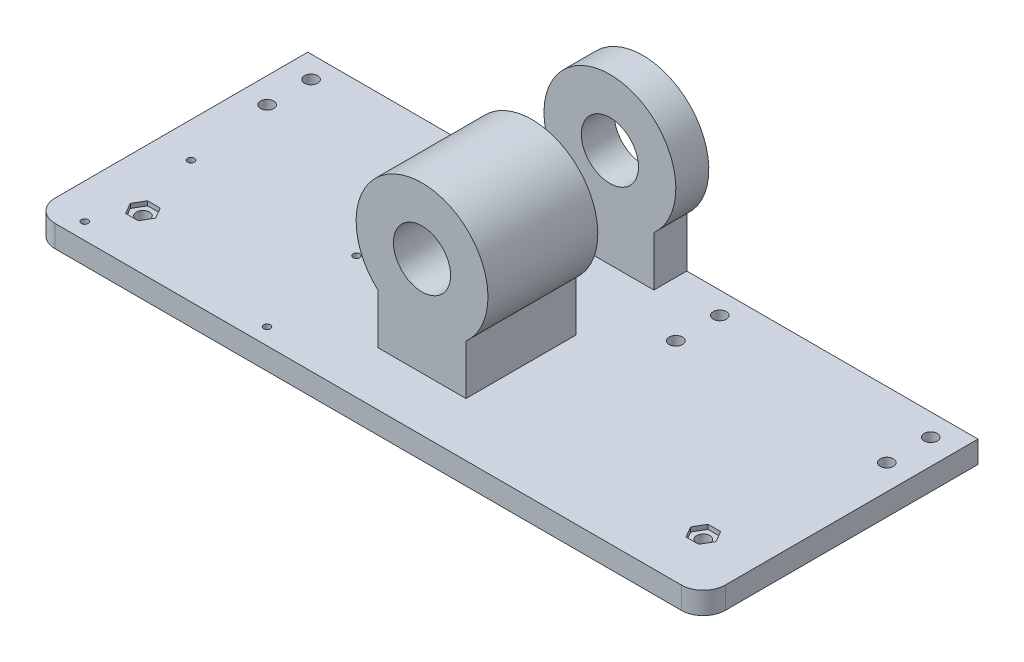
SolidWorks part; units mm, degrees
ref_plane "Front Plane" through (0, 0, 0) normal (0, 0, 1) x (1, 0, 0)
ref_plane "Top Plane" through (0, 0, 0) normal (0, 1, 0) x (1, 0, 0)
ref_plane "Right Plane" through (0, 0, 0) normal (1, 0, 0) x (0, 0, -1)
sketch "Sketch1" plane through (0, 0, 0) normal (0, 1, 0) x (1, 0, 0)
  line L0 (152.5, 125) -> (152.5, 0) construction
  line L1 (0, 0) -> (305, 0)
  line L2 (0, 0) -> (0, 125)
  line L3 (0, 125) -> (305, 125)
  line L4 (305, 0) -> (305, 125)
  line L5 (25, 100) -> (280, 100) construction
  line L6 (280, 25) -> (280, 100) construction
  line L7 (25, 25) -> (280, 25) construction
  line L8 (25, 25) -> (25, 100) construction
  line L9 (152.5, 62.5) -> (25, 62.5) construction
  line L10 (30.7735, 100) -> (27.8868, 105) construction
  line L11 (27.8868, 105) -> (22.1132, 105) construction
  line L12 (22.1132, 105) -> (19.2265, 100) construction
  line L13 (19.2265, 100) -> (22.1132, 95) construction
  line L14 (22.1132, 95) -> (27.8868, 95) construction
  line L15 (27.8868, 95) -> (30.7735, 100) construction
  line L16 (27.8868, 30) -> (30.7735, 25) construction
  line L17 (22.1132, 30) -> (27.8868, 30) construction
  line L18 (19.2265, 25) -> (22.1132, 30) construction
  line L19 (22.1132, 20) -> (19.2265, 25) construction
  line L20 (27.8868, 20) -> (22.1132, 20) construction
  line L21 (30.7735, 25) -> (27.8868, 20) construction
  line L22 (282.8868, 30) -> (277.1132, 30) construction
  line L23 (285.7735, 25) -> (282.8868, 30) construction
  line L24 (282.8868, 20) -> (285.7735, 25) construction
  line L25 (277.1132, 20) -> (282.8868, 20) construction
  line L26 (274.2265, 25) -> (277.1132, 20) construction
  line L27 (277.1132, 30) -> (274.2265, 25) construction
  line L28 (277.1132, 95) -> (274.2265, 100) construction
  line L29 (282.8868, 95) -> (277.1132, 95) construction
  line L30 (285.7735, 100) -> (282.8868, 95) construction
  line L31 (282.8868, 105) -> (285.7735, 100) construction
  line L32 (277.1132, 105) -> (282.8868, 105) construction
  line L33 (274.2265, 100) -> (277.1132, 105) construction
  line L34 (107.5, 115) -> (107.5, 125) construction
  line L35 (132.5, 0) -> (172.5, 0) construction
  line L37 (132.5, 125) -> (172.5, 125) construction
  line L41 (132.5, 25) -> (172.5, 25) construction
  line L50 (305, 14.5) -> (253.3, 14.5) construction
  line L51 (30.7735, 100) -> (22.1132, 105) construction
  line L54 (0, 125) -> (90.0836, 125) construction
  line L55 (0, 125) -> (0, 84.5) construction
  line L62 (0, 84.5) -> (0, 69.5) construction
  line L64 (62, 0) -> (62, 125) construction
  line L65 (253.3, 14.5) -> (253.3, 0) construction
  line L67 (253.3, 14.5) -> (280.2, 14.5) construction
  circle A1 centre (25, 100) radius 5 construction
  circle A3 centre (280, 25) radius 3
  circle A4 centre (25, 25) radius 3
  circle A18 centre (107.5, 115) radius 3
  circle A20 centre (107.5, 95) radius 3
  circle A23 centre (197.5, 115) radius 3
  circle A24 centre (197.5, 95) radius 3
  circle A27 centre (107.5, 75) radius 3 [skipped]
  circle A28 centre (107.5, 55) radius 3 [skipped]
  circle A29 centre (11.5, 95) radius 3
  circle A30 centre (11.5, 115) radius 3
  circle A31 centre (293.5, 115) radius 3
  circle A32 centre (293.5, 95) radius 3
  dimension "D3" = 6
  dimension "D1" = 305
  dimension "D2" = 125
  dimension "D5" = 10
  dimension "D6" = 40
  dimension "D15" = 62
  dimension "D18" = 51.7
  dimension "D19" = 14.5
  dimension "D20" = 26.9
  dimension "D8" = 20
  dimension "D9" = 45
  dimension "D11" = 11.5
  dimension "D4" = 25
  dimension "D14" = 2
  dimension "D7" = 4
  dimension "D10" = 2
extrude "Boss-Extrude1" add sketch "Sketch1" along normal blind 10
sketch "Sketch7" plane through (0, 10, 0) normal (0, 1, 0) x (1, 0, 0)
  line L0 (0, 0) -> (305, 0) construction
  line L1 (132.5, 24.5) -> (172.5, 24.5)
  line L2 (132.5, 24.5) -> (132.5, 74.5)
  line L3 (132.5, 74.5) -> (172.5, 74.5)
  line L4 (172.5, 24.5) -> (172.5, 74.5)
  line L5 (152.5, 0) -> (152.5, 125) construction
  line L6 (305, 125) -> (0, 125) construction
  line L18 (132.5, 110) -> (172.5, 110)
  line L19 (132.5, 110) -> (132.5, 125)
  line L20 (132.5, 125) -> (172.5, 125)
  line L21 (172.5, 110) -> (172.5, 125)
  point P11 (152.5, 74.5)
  point P20 (152.5, 110)
  dimension "D1" = 40
  dimension "D2" = 50
  dimension "D4" = 15
  dimension "D3" = 35.5
extrude "Boss-Extrude2" add sketch "Sketch7" along normal blind 22.6393
sketch "Sketch11" plane through (0, 0, -24.5) normal (0, 0, 1) x (1, 0, 0)
  circle A0 centre (152.5, 55) radius 30
  circle A1 centre (152.5, 55) radius 13
  dimension "D1" = 60
  dimension "D2" = 26
extrude "Boss-Extrude3" add sketch "Sketch11" against normal up to surface (100.5 mm away) up to face at (152.5, 13.1598, -125)
ref_plane "Plane1" through (0, 0, -62.5) normal (0, 0, 1) x (1, 0, 0)
sketch "Sketch12" plane through (305, 0, 0) normal (1, 0, 0) x (0, 0, -1)
  line L0 (125, 85) -> (24.5, 85) construction
  line L1 (74.5, 10) -> (110, 10)
  line L2 (74.5, 10) -> (74.5, 85)
  line L3 (74.5, 85) -> (110, 85)
  line L4 (110, 10) -> (110, 85)
  line L6 (110, 32.6393) -> (110, 10) construction
extrude "Cut-Extrude2" cut sketch "Sketch12" against normal through all
sketch "Sketch6" plane through (0, 10, 0) normal (0, 1, 0) x (1, 0, 0)
  line L0 (152.5, 125) -> (152.5, 0) construction
  line L8 (0, 0) -> (305, 0) construction
  line L9 (152.5, 62.5) -> (0, 62.5) construction
  line L10 (0, 125) -> (0, 0) construction
  line L29 (27.8868, 30) -> (30.7735, 25)
  line L30 (274.2265, 25) -> (277.1132, 20)
  line L31 (277.1132, 20) -> (282.8868, 20)
  line L32 (282.8868, 20) -> (285.7735, 25)
  line L33 (285.7735, 25) -> (282.8868, 30)
  line L34 (282.8868, 30) -> (277.1132, 30)
  line L35 (277.1132, 30) -> (274.2265, 25)
  line L36 (22.1132, 30) -> (27.8868, 30)
  line L37 (19.2265, 25) -> (22.1132, 30)
  line L38 (22.1132, 20) -> (19.2265, 25)
  line L39 (27.8868, 20) -> (22.1132, 20)
  line L40 (30.7735, 25) -> (27.8868, 20)
  circle A0 centre (280, 25) radius 5 construction
  dimension "D1" = 10
extrude "Cut-Extrude1" cut sketch "Sketch6" against normal blind 2
sketch "Sketch16" plane through (0, 10, 0) normal (0, 1, 0) x (1, 0, 0)
  line L0 (0, 0) -> (305, 0) construction
  line L1 (0, 125) -> (0, 0) construction
  circle A0 centre (16, 7.5) radius 1.55
  circle A1 centre (98.95, 7.5) radius 1.55
  circle A2 centre (16, 55.866) radius 1.55
  circle A3 centre (91.33, 55.866) radius 1.55
  dimension "D1" = 3.1
  dimension "D2" = 7.5
  dimension "D3" = 82.95
  dimension "D4" = 16
  dimension "D5" = 48.366
  dimension "D6" = 75.33
extrude "Cut-Extrude3" cut sketch "Sketch16" against normal through all
fillet "Fillet3" radius 10 2 edges at (305, 5, 0) (0, 5, 0)
chamfer "Chamfer2" distance 1.65 4 edges at (98.95, 0, -5.95) (91.33, 0, -54.316) (16, 0, -5.95) (16, 0, -54.316)
equation "\"joint_width\"=4"
equation "\"short_base_length\"=12.5"
equation "\"D2@Sketch1\"=\"short_base_length\""
equation "\"outer_diam_main_joint\"=6"
equation "\"D1@Sketch11\"=\"outer_diam_main_joint\""
equation "\"D1@Sketch7\"=\"outer_diam_main_joint\"-2"
equation "\"D1@Boss-Extrude2\"=(\"outer_diam_main_joint\"/2)+1.5cm-sqr((\"outer_diam_main_joint\"/2)^2-((\"outer_diam_main_joint\"-2)/2)^2)"
equation "\"D6@Sketch1\"=\"outer_diam_main_joint\"-2"
equation "\"pulleyside\"=1.5"
